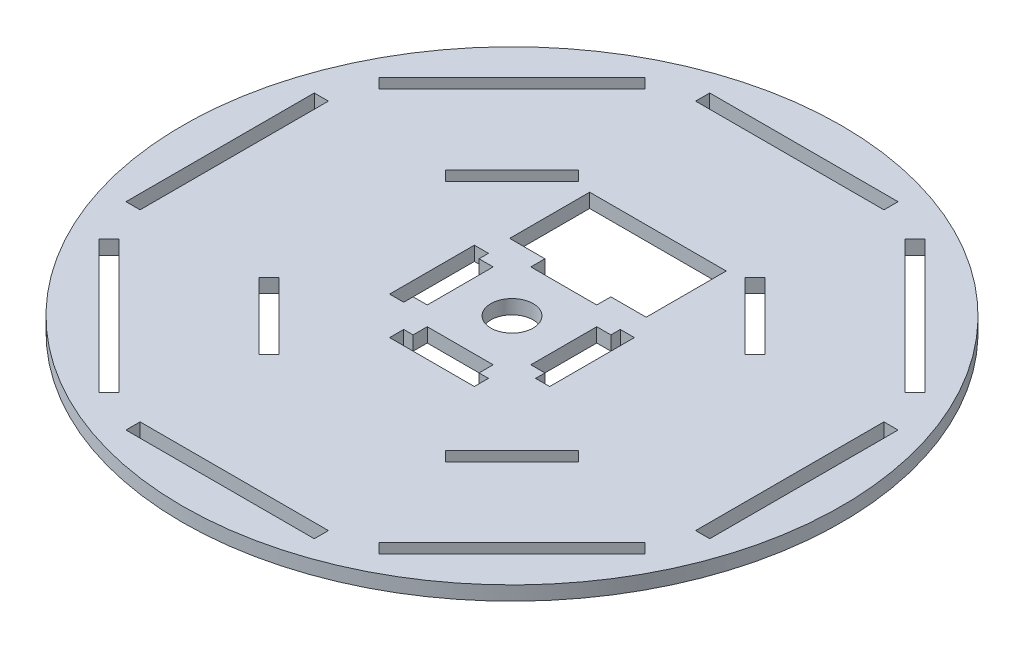
SolidWorks part; units mm, degrees
ref_plane "Alzado" through (0, 0, 0) normal (0, 0, 1) x (1, 0, 0)
ref_plane "Planta" through (0, 0, 0) normal (0, 1, 0) x (1, 0, 0)
ref_plane "Vista lateral" through (0, 0, 0) normal (1, 0, 0) x (0, 0, -1)
sketch "Croquis1" plane through (0, 0, 0) normal (0, 1, 0) x (1, 0, 0)
  line L0 (0, 11) -> (7, 11)
  line L1 (7, 11) -> (7, 14)
  line L2 (24.7487, 24.7487) -> (31.8198, 17.6777)
  line L3 (-7, 14) -> (-7, 11)
  line L4 (-7, 11) -> (0, 11)
  line L5 (11, 0) -> (11, 7)
  line L6 (11, 7) -> (14, 7)
  line L7 (-70, 0) -> (70, 0) construction
  line L8 (14, -7) -> (11, -7)
  line L9 (11, -7) -> (11, 0)
  line L10 (0, 0) -> (-24.7487, 24.7487) construction
  line L11 (-24.7487, 24.7487) -> (-17.6777, 31.8198)
  line L12 (-17.6777, 31.8198) -> (-19.799, 33.9411)
  line L13 (-14, -7) -> (-11, -7)
  line L14 (-11, -7) -> (-11, 0)
  line L15 (-11, 0) -> (-11, 7)
  line L16 (-11, 7) -> (-14, 7)
  line L17 (-7, -14) -> (-9, -14)
  line L18 (7, -11) -> (7, -14)
  line L19 (0, -11) -> (7, -11)
  line L20 (14, -7) -> (14, -9)
  line L21 (-7, -14) -> (-7, -11)
  line L22 (-7, -11) -> (0, -11)
  line L23 (-19.799, 33.9411) -> (-33.9411, 19.799)
  line L24 (-24.7487, 24.7487) -> (-31.8198, 17.6777)
  line L25 (-31.8198, 17.6777) -> (-33.9411, 19.799)
  line L26 (7, 14) -> (14.5, 14)
  line L27 (14.5, 14) -> (14.5, 31)
  line L28 (14.5, 31) -> (-14.5, 31)
  line L29 (-14.5, 31) -> (-14.5, 14)
  line L30 (-14.5, 14) -> (-7, 14)
  line L31 (31.8198, 17.6777) -> (33.9411, 19.799)
  line L32 (33.9411, 19.799) -> (19.799, 33.9411)
  line L33 (17.6777, 31.8198) -> (19.799, 33.9411)
  line L34 (24.7487, 24.7487) -> (17.6777, 31.8198)
  line L35 (24.7487, -24.7487) -> (17.6777, -31.8198)
  line L36 (17.6777, -31.8198) -> (19.799, -33.9411)
  line L37 (19.799, -33.9411) -> (33.9411, -19.799)
  line L38 (31.8198, -17.6777) -> (33.9411, -19.799)
  line L39 (24.7487, -24.7487) -> (31.8198, -17.6777)
  line L40 (-24.7487, -24.7487) -> (-31.8198, -17.6777)
  line L41 (0, 0) -> (0, 62) construction
  line L42 (0, 62) -> (20, 62)
  line L43 (20, 62) -> (20, 59)
  line L44 (20, 59) -> (-20, 59)
  line L45 (-20, 59) -> (-20, 62)
  line L46 (-20, 62) -> (0, 62)
  line L47 (55.8614, 27.5772) -> (27.5772, 55.8614)
  line L48 (27.5772, 55.8614) -> (29.6985, 57.9828)
  line L49 (29.6985, 57.9828) -> (43.8406, 43.8406)
  line L50 (43.8406, 43.8406) -> (57.9828, 29.6985)
  line L51 (57.9828, 29.6985) -> (55.8614, 27.5772)
  line L52 (59, -20) -> (59, 20)
  line L53 (59, 20) -> (62, 20)
  line L54 (62, 20) -> (62, 0)
  line L55 (62, 0) -> (62, -20)
  line L56 (62, -20) -> (59, -20)
  line L57 (27.5772, -55.8614) -> (55.8614, -27.5772)
  line L58 (55.8614, -27.5772) -> (57.9828, -29.6985)
  line L59 (57.9828, -29.6985) -> (43.8406, -43.8406)
  line L60 (43.8406, -43.8406) -> (29.6985, -57.9828)
  line L61 (29.6985, -57.9828) -> (27.5772, -55.8614)
  line L62 (-20, -59) -> (20, -59)
  line L63 (20, -59) -> (20, -62)
  line L64 (20, -62) -> (0, -62)
  line L65 (0, -62) -> (-20, -62)
  line L66 (-20, -62) -> (-20, -59)
  line L67 (-55.8614, -27.5772) -> (-27.5772, -55.8614)
  line L68 (-27.5772, -55.8614) -> (-29.6985, -57.9828)
  line L69 (-29.6985, -57.9828) -> (-43.8406, -43.8406)
  line L70 (-43.8406, -43.8406) -> (-57.9828, -29.6985)
  line L71 (-57.9828, -29.6985) -> (-55.8614, -27.5772)
  line L72 (-59, 20) -> (-59, -20)
  line L73 (-59, -20) -> (-62, -20)
  line L74 (-62, -20) -> (-62, 0)
  line L75 (-62, 0) -> (-62, 20)
  line L76 (-62, 20) -> (-59, 20)
  line L77 (-27.5772, 55.8614) -> (-55.8614, 27.5772)
  line L78 (-55.8614, 27.5772) -> (-57.9828, 29.6985)
  line L79 (-57.9828, 29.6985) -> (-43.8406, 43.8406)
  line L80 (-43.8406, 43.8406) -> (-29.6985, 57.9828)
  line L81 (-29.6985, 57.9828) -> (-27.5772, 55.8614)
  line L82 (-31.8198, -17.6777) -> (-33.9411, -19.799)
  line L83 (-33.9411, -19.799) -> (-19.799, -33.9411)
  line L84 (-17.6777, -31.8198) -> (-19.799, -33.9411)
  line L85 (-24.7487, -24.7487) -> (-17.6777, -31.8198)
  line L86 (-14, 7) -> (-14, 9)
  line L87 (-14, 9) -> (-17, 9)
  line L88 (-17, 9) -> (-17, -9)
  line L89 (-17, -9) -> (-14, -9)
  line L90 (-14, -9) -> (-14, -7)
  line L92 (0, -17) -> (9, -17)
  line L93 (9, -17) -> (9, -14)
  line L94 (9, -14) -> (7, -14)
  line L95 (-9, -14) -> (-9, -17)
  line L96 (-9, -17) -> (0, -17)
  line L98 (17, 0) -> (17, 9)
  line L99 (17, 9) -> (14, 9)
  line L100 (14, 9) -> (14, 7)
  line L101 (14, -9) -> (17, -9)
  line L102 (17, -9) -> (17, 0)
  circle A0 centre (0, 0) radius 4.5
  circle A2 centre (0, 0) radius 70
  point P47 (0, 0)
  point P88 (0, 0)
  point P93 (0, 0)
  dimension "D1" = 9
  dimension "D2" = 14
  dimension "D3" = 140
  dimension "D4" = 7
  dimension "D5" = 3
  dimension "D6" = 14
  dimension "D7" = 35
  dimension "D8" = 3
  dimension "D9" = 10
  dimension "D10" = 3
  dimension "D11" = 20
  dimension "D12" = 10
  dimension "D14" = 62
  dimension "D15" = 20
  dimension "D16" = 3
  dimension "D17" = 40
  dimension "D19" = 17
  dimension "D13" = 4
  dimension "D20" = 29
  dimension "D21" = 3
  dimension "D23" = 3
  dimension "D24" = 18
  dimension "D26" = 9
  dimension "D27" = 18
  dimension "D29" = 9
  dimension "D18" = 8
extrude "Saliente-Extruir1" add sketch "Croquis1" along normal blind 3
